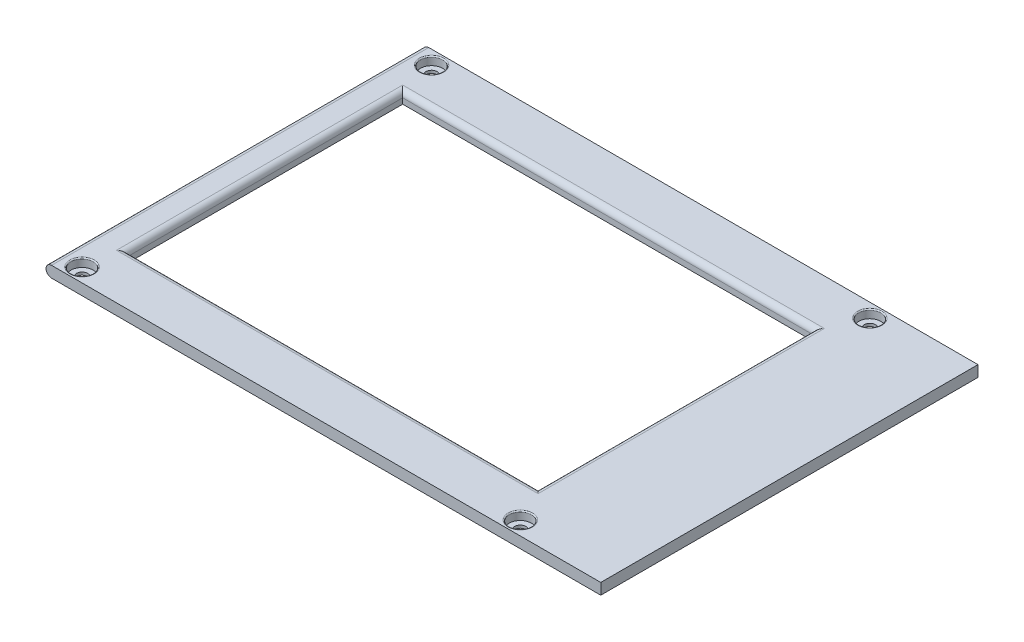
SolidWorks part; units mm, degrees
material "ПК/АБС"
ref_plane "Спереди" through (0, 0, 0) normal (0, 0, 1) x (1, 0, 0)
ref_plane "Сверху" through (0, 0, 0) normal (0, 1, 0) x (1, 0, 0)
ref_plane "Справа" through (0, 0, 0) normal (1, 0, 0) x (0, 0, -1)
sketch "Эскиз1" plane through (0, 0, 0) normal (0, 1, 0) x (1, 0, 0)
  line L1 (50, -34) -> (-50, -34)
  line L2 (50, -34) -> (50, 34)
  line L3 (50, 34) -> (-50, 34)
  line L4 (-50, -34) -> (-50, 34)
  line L5 (50, -34) -> (-50, 34) construction
  line L6 (50, 34) -> (-50, -34) construction
  point P0 (0, 0)
extrude "Бобышка-Вытянуть1" add sketch "Эскиз1" along normal blind 2
sketch "Эскиз2" plane through (0, 2, 0) normal (0, 1, 0) x (1, 0, 0)
  circle A0 centre (-46, 31.5) radius 1
  circle A1 centre (33, 31.5) radius 1
  circle A2 centre (33, -31.5) radius 1
  circle A3 centre (-46, -31.5) radius 1
extrude "Вырез-Вытянуть1" cut sketch "Эскиз2" against normal blind 2
sketch "Эскиз3" plane through (0, 2, 0) normal (0, 1, 0) x (1, 0, 0)
  circle A0 centre (-46, 31.5) radius 2
  circle A1 centre (-46, -31.5) radius 2
  circle A2 centre (33, -31.5) radius 2
  circle A3 centre (33, 31.5) radius 2
extrude "Вырез-Вытянуть2" cut sketch "Эскиз3" against normal blind 1.5
sketch "Эскиз4" plane through (0, 2, 0) normal (0, 1, 0) x (1, 0, 0)
  line L8 (-44.5, 24.8) -> (29.5, 24.8)
  line L9 (-44.5, 24.8) -> (-44.5, -24.8)
  line L14 (-44.5, -24.8) -> (29.5, -24.8)
  line L15 (29.5, 24.8) -> (29.5, -24.8)
extrude "Вырез-Вытянуть3" cut sketch "Эскиз4" against normal blind 5
fillet "Скругление1" radius 1 3 edges at (-7.5, 2, -24.8) (-50, 2, 0) (-50, 0, 0)
fillet "Скругление2" radius 1 3 edges at (-44.5, 2, -0.5) (-7.5, 2, 24.8) (29.5, 2, -0.5)
fillet "Скругление3" radius 0.2 4 edges at (33, 2, 33.5) (33, 2, -29.5) (-46, 2, -29.5) (-46, 2, 33.5)
